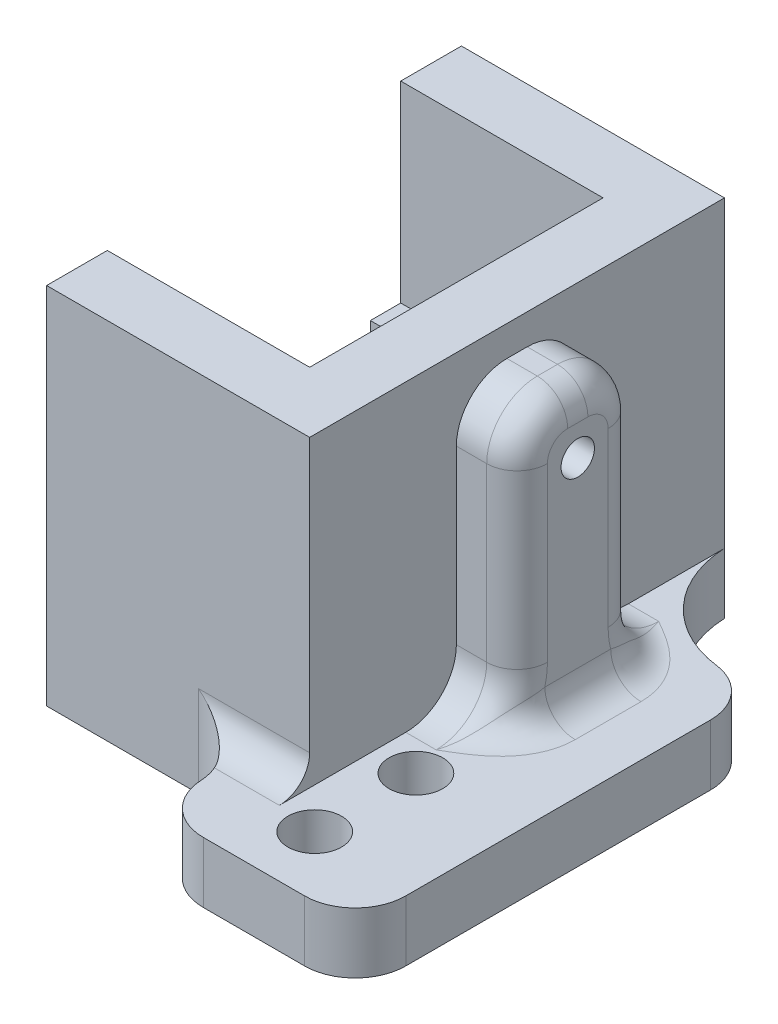
SolidWorks part; units mm, degrees
ref_plane "Front Plane" through (0, 0, 0) normal (0, 0, 1) x (1, 0, 0)
ref_plane "Top Plane" through (0, 0, 0) normal (0, 1, 0) x (1, 0, 0)
ref_plane "Right Plane" through (0, 0, 0) normal (1, 0, 0) x (0, 0, -1)
sketch "Sketch1" plane through (0, 0, 0) normal (0, 1, 0) x (1, 0, 0)
  line L1 (0, 0) -> (40, 0)
  line L2 (0, 0) -> (0, -20)
  line L3 (0, -20) -> (20, -20)
  line L4 (40, 0) -> (40, -20)
  line L6 (40, -20) -> (40, -40)
  line L7 (40, -40) -> (20, -40)
  line L8 (20, -20) -> (20, -40)
  dimension "D1" = 20
  dimension "D2" = 40
  dimension "D3" = 20
  dimension "D4" = 20
extrude "Boss-Extrude1" add sketch "Sketch1" along normal blind 6
sketch "Sketch2" plane through (0, 6, 0) normal (0, 1, 0) x (1, 0, 0)
  line L0 (40, 0) -> (0, 0) construction
  line L1 (0, 0) -> (0, -20) construction
  line L2 (20, -40) -> (40, -40) construction
  line L3 (20, -20) -> (20, -40) construction
  circle A0 centre (6, -10) radius 2.65
  circle A1 centre (16, -10) radius 2.65
  circle A2 centre (30, -34) radius 2.65
  circle A3 centre (30, -24) radius 2.65
  dimension "D1" = 5.3
  dimension "D5" = 5.3
  dimension "D2" = 10
  dimension "D3" = 6
  dimension "D6" = 6
  dimension "D7" = 10
  dimension "D8" = 2
extrude "Cut-Extrude1" cut sketch "Sketch2" against normal through all
sketch "Sketch3" plane through (0, 6, 0) normal (0, 1, 0) x (1, 0, 0)
  line L0 (0, -10) -> (31.6362, -10) construction
  line L1 (0, 0) -> (20, 0)
  line L2 (0, 0) -> (0, 10.5)
  line L3 (0, 10.5) -> (20, 10.5)
  line L4 (20, 0) -> (20, 10.5)
  line L5 (0, 0) -> (0, -20) construction
  line L6 (0, -20) -> (20, -20)
  line L7 (0, -20) -> (0, -30.5)
  line L8 (0, -30.5) -> (20, -30.5)
  line L9 (20, -20) -> (20, -30.5)
  dimension "D1" = 10.5
  dimension "D2" = 20
extrude "Boss-Extrude2" add sketch "Sketch3" against normal blind 6
sketch "Sketch4" plane through (0, 6, 0) normal (0, 1, 0) x (1, 0, 0)
  line L0 (0, 10.5) -> (0, -30.5) construction
  line L1 (20, 10.5) -> (0, 10.5)
  line L2 (20, 10.5) -> (20, 4.5)
  line L3 (20, 4.5) -> (0, 4.5)
  line L4 (0, 10.5) -> (0, 4.5)
  line L6 (0, -30.5) -> (20, -30.5)
  line L7 (0, -30.5) -> (0, -24.5)
  line L8 (0, -24.5) -> (20, -24.5)
  line L9 (20, -30.5) -> (20, -24.5)
  dimension "D1" = 6
  dimension "D2" = 6
extrude "Boss-Extrude3" add sketch "Sketch4" along normal blind 30
sketch "Sketch7" plane through (0, 0, 0) normal (0, 0, -1) x (-1, 0, 0)
  line L0 (-40, 0) -> (-20, 0) construction
  line L1 (-20, 6) -> (-26, 6)
  line L2 (-20, 6) -> (-20, 0)
  line L3 (-20, 0) -> (-26, 0)
  line L4 (-26, 6) -> (-26, 0)
  dimension "D1" = 6
extrude "Boss-Extrude7" add sketch "Sketch7" along normal blind 10.5
sketch "Sketch6" plane through (0, 6, 0) normal (0, 1, 0) x (1, 0, 0)
  line L1 (20, -30.5) -> (26, -30.5)
  line L2 (20, -30.5) -> (20, 10.5)
  line L3 (20, 10.5) -> (26, 10.5)
  line L4 (26, -30.5) -> (26, 10.5)
  dimension "D1" = 6
  dimension "D2" = 41
extrude "Boss-Extrude8" add sketch "Sketch6" along normal blind 30
sketch "Sketch8" plane through (20, 0, 0) normal (-1, 0, 0) x (0, 0, 1)
  line L0 (-4.5, 6) -> (24.5, 6) construction
  circle A0 centre (10, 27) radius 1.65
  dimension "D1" = 3.3
  dimension "D2" = 21
extrude "Cut-Extrude2" cut sketch "Sketch8" against normal through all
sketch "Sketch9" plane through (20, 0, 0) normal (-1, 0, 0) x (0, 0, 1)
  line L1 (24.5, 6) -> (21.5, 6)
  line L2 (24.5, 6) -> (24.5, 17)
  line L3 (24.5, 17) -> (21.5, 17)
  line L4 (21.5, 6) -> (21.5, 17)
  line L5 (-4.5, 6) -> (-1.5, 6)
  line L6 (-4.5, 6) -> (-4.5, 17)
  line L7 (-4.5, 17) -> (-1.5, 17)
  line L8 (-1.5, 6) -> (-1.5, 17)
  circle A0 centre (10, 27) radius 1.65 construction
  dimension "D2" = 10
extrude "Boss-Extrude9" add sketch "Sketch9" along normal blind 20
fillet "Fillet1" radius 11 1 edges at (26, 3, 0)
fillet "Fillet3" radius 5 1 edges at (20, 3, 30.5)
fillet "Fillet4" radius 5 3 edges at (20, 3, 40) (40, 3, 40) (40, 3, 0)
fillet "Fillet5" radius 3 1 edges at (20.5, 6, 30.5)
sketch "Sketch11" plane through (26, 0, 0) normal (1, 0, 0) x (0, 0, -1)
  line L0 (-33.5, 6) -> (10.5, 6) construction
  line L1 (-16, 6) -> (-4, 6)
  line L2 (-16, 6) -> (-16, 33)
  line L3 (-16, 33) -> (-4, 33)
  line L4 (-4, 6) -> (-4, 33)
  circle A0 centre (-10, 27) radius 1.65 construction
  circle A1 centre (-10, 27) radius 1.65
  dimension "D4" = 3.3
  dimension "D1" = 12
  dimension "D2" = 6
  dimension "D3" = 27
extrude "Boss-Extrude10" add sketch "Sketch11" along normal blind 6
fillet "Fillet7" radius 5 4 edges at (29, 6, 4) (29, 6, 16) (29, 33, 16) (29, 33, 4)
fillet "Fillet8" radius 3 8 edges at (32, 19.5, 4) (32, 7.4645, 2.5355) (32, 6, 10) (32, 7.4645, 17.4645) (32, 19.5, 16) (32, 31.5355, 5.4645) (32, 31.5355, 14.5355) (32, 33, 10)
ref_plane "打印面" through (0, -10, 0) normal (0, -1, 0) x (-1, 0, 0)
equation "\"滑动-垂直孔\"= 0.6"
equation "\"滑动-水平孔\"= 0.3"
equation "\"松动-垂直孔\"= 0.3"
equation "\"松动-水平孔\"= 0.1"
equation "\"正常-垂直孔\"= 0.15"
equation "\"正常-水平孔\"= 0"
equation "\"紧缩-垂直孔\"= 0"
equation "\"紧缩-水平孔\"= - 0.1"
equation "\"D1@Sketch2\"=\"松动-垂直孔\"+5"
equation "\"D2@Sketch2\"=\"D1@Sketch1\"/2"
equation "\"D5@Sketch2\"=\"D1@Sketch2\""
equation "\"D6@Sketch2\"=\"D3@Sketch2\""
equation "\"D7@Sketch2\"=\"D2@Sketch2\""
equation "\"D1@Sketch3\"=(28+1+12-20)/2"
equation "\"D2@Sketch3\"=15+5"
equation "\"D1@Sketch8\"=\"松动-垂直孔\"+3"
equation "\"D2@Sketch9\"=\"D1@Sketch9\""
equation "\"D4@Sketch9\"=\"D3@Sketch9\""
equation "\"D2@Sketch11\"=\"D1@Sketch11\"/2"
equation "\"D4@Sketch11\"=\"D1@Sketch8\""
